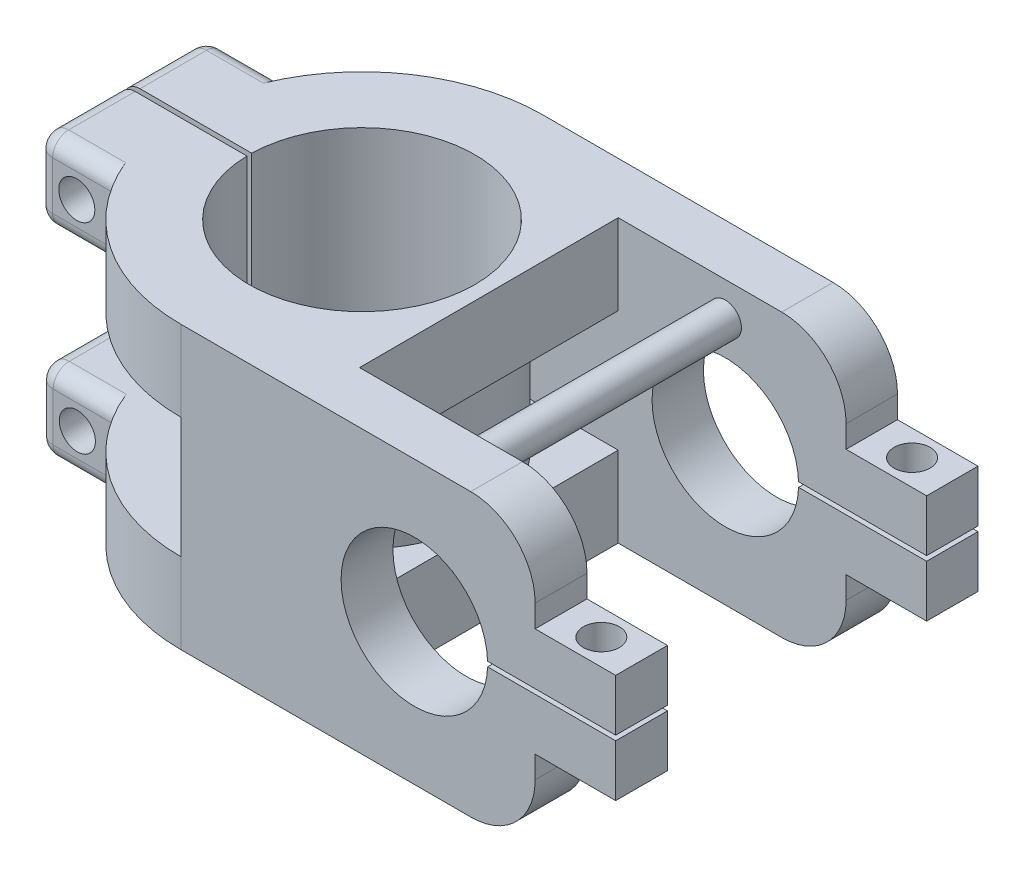
SolidWorks part; units mm, degrees
ref_plane "Front Plane" through (0, 0, 0) normal (0, 0, 1) x (1, 0, 0)
ref_plane "Top Plane" through (0, 0, 0) normal (0, 1, 0) x (1, 0, 0)
ref_plane "Right Plane" through (0, 0, 0) normal (1, 0, 0) x (0, 0, -1)
sketch "Sketch2" plane through (0, 0, 0) normal (0, 1, 0) x (1, 0, 0)
  circle A0 centre (0, 0) radius 17.78
  circle A2 centre (0, 0) radius 28.575
  dimension "D1" = 35.56
  dimension "D2" = 57.15
extrude "Boss-Extrude3" add sketch "Sketch2" along normal blind 12.7
sketch "Sketch3" plane through (0, 12.7, 0) normal (0, 1, 0) x (1, 0, 0)
  line L0 (0, 0) -> (20.2056, -20.2056) construction
  line L1 (0, 0) -> (20.2056, 20.2056) construction
  line L2 (0, 0) -> (-28.575, 0) construction
  line L3 (-25.3321, 0) -> (-25.3321, 13.2218) construction
  line L4 (-25.3321, 13.2218) -> (-25.3321, -13.2218)
  line L5 (-25.3321, 13.2218) -> (-36.1866, 13.2218)
  line L6 (-36.1866, 13.2218) -> (-36.1866, -13.2218)
  line L7 (-36.1866, -13.2218) -> (-25.3321, -13.2218)
  circle A0 centre (0, 0) radius 28.575 construction
extrude "Cut-Extrude1" cut sketch "Sketch3" against normal blind 12.7
sketch "Sketch4" plane through (0, 12.7, 0) normal (0, 1, 0) x (1, 0, 0)
  line L0 (0, 0) -> (-25.3321, 0) construction
  line L1 (-25.3321, -13.2218) -> (-25.3321, 13.2218) construction
  line L2 (-16.3768, 0) -> (-16.3768, 0.381)
  line L3 (-16.3768, 0) -> (-16.3768, -0.381)
  line L4 (-16.3768, 0.381) -> (-26.0036, 0.381)
  line L5 (-16.3768, -0.381) -> (-26.0036, -0.381)
  line L6 (-26.0036, -0.381) -> (-26.0036, 0.381)
  dimension "D1" = 0.762
extrude "Cut-Extrude2" cut sketch "Sketch4" against normal blind 12.7
sketch "Sketch5" plane through (-25.3321, 0, 0) normal (-1, 0, 0) x (0, 0, 1)
  line L1 (0.381, 12.7) -> (13.2218, 12.7)
  line L2 (0.381, 12.7) -> (0.381, 0)
  line L3 (0.381, 0) -> (13.2218, 0)
  line L4 (13.2218, 12.7) -> (13.2218, 0)
extrude "Boss-Extrude4" add sketch "Sketch5" along normal blind 12.7
sketch "Sketch6" plane through (-25.3321, 0, 0) normal (-1, 0, 0) x (0, 0, 1)
  line L1 (-13.2218, 12.7) -> (-0.381, 12.7)
  line L2 (-13.2218, 12.7) -> (-13.2218, 0)
  line L3 (-13.2218, 0) -> (-0.381, 0)
  line L4 (-0.381, 12.7) -> (-0.381, 0)
extrude "Boss-Extrude5" add sketch "Sketch6" along normal blind 12.7
sketch "Sketch7" plane through (0, 0, 13.2218) normal (0, 0, 1) x (1, 0, 0)
  line L0 (-31.6821, 12.7) -> (-31.6821, 0) construction
  line L1 (-38.0321, 12.7) -> (-25.3321, 12.7) construction
  line L2 (-38.0321, 0) -> (-25.3321, 0) construction
  circle A0 centre (-31.6821, 6.35) radius 2.8448
extrude "Cut-Extrude3" cut sketch "Sketch7" against normal blind 33.02
fillet "Fillet1" radius 2.54 1 edges at (-38.0321, 6.35, 13.2218)
fillet "Fillet2" radius 2.54 1 edges at (-38.0321, 6.35, -13.2218)
fillet "Fillet3" radius 2.54 3 edges at (-30.4121, 12.7, -13.2218) (-37.2882, 12.7, -12.4778) (-38.0321, 12.7, -5.5314)
fillet "Fillet4" radius 2.54 3 edges at (-30.4121, 12.7, 13.2218) (-37.2882, 12.7, 12.4778) (-38.0321, 12.7, 5.5314)
fillet "Fillet5" radius 2.54 3 edges at (-30.4121, 0, -13.2218) (-37.2882, 0, -12.4778) (-38.0321, 0, -5.5314)
fillet "Fillet6" radius 2.54 3 edges at (-30.4121, 0, 13.2218) (-37.2882, 0, 12.4778) (-38.0321, 0, 5.5314)
sketch "Sketch8" plane through (0, 12.7, 0) normal (0, 1, 0) x (1, 0, 0)
  circle A0 centre (0, 0) radius 18.7388
  circle A1 centre (0, 0) radius 17.78
extrude "Boss-Extrude6" add sketch "Sketch8" along normal blind 19.05
sketch "Sketch9" plane through (0, 31.75, 0) normal (0, 1, 0) x (1, 0, 0)
  circle A0 centre (0, 0) radius 28.575
extrude "Boss-Extrude7" add sketch "Sketch9" along normal blind 12.7
sketch "Sketch12" plane through (0, 44.45, 0) normal (0, 1, 0) x (1, 0, 0)
  line L0 (0, 0) -> (-28.575, 0) construction
  line L1 (-25.2365, 13.4034) -> (-25.2365, -13.4034)
  line L2 (-25.2365, 13.4034) -> (-36.6122, 13.4034)
  line L3 (-25.2365, -13.4034) -> (-36.6122, -13.4034)
  line L4 (-36.6122, -13.4034) -> (-36.6122, 13.4034)
  circle A0 centre (0, 0) radius 28.575 construction
extrude "Cut-Extrude4" cut sketch "Sketch12" against normal blind 12.7
sketch "Sketch13" plane through (-25.2365, 0, 0) normal (-1, 0, 0) x (0, 0, 1)
  line L0 (-18.7388, 31.75) -> (18.7388, 31.75) construction
  line L1 (-13.4034, 44.45) -> (13.4034, 44.45)
  line L2 (-13.4034, 44.45) -> (-13.4034, 31.75)
  line L3 (-13.4034, 31.75) -> (13.4034, 31.75)
  line L4 (13.4034, 44.45) -> (13.4034, 31.75)
  line L5 (13.4034, 31.75) -> (-13.4034, 31.75) construction
extrude "Boss-Extrude8" add sketch "Sketch13" along normal blind 12.7
sketch "Sketch14" plane through (0, 44.45, 0) normal (0, 1, 0) x (1, 0, 0)
  circle A0 centre (0, 0) radius 17.78
extrude "Cut-Extrude5" cut sketch "Sketch14" against normal blind 12.7
sketch "Sketch15" plane through (0, 44.45, 0) normal (0, 1, 0) x (1, 0, 0)
  line L0 (-37.9365, 0) -> (0, 0)
  line L1 (-37.9365, -13.4034) -> (-37.9365, 13.4034) construction
  line L2 (0, 0) -> (0, 0.381)
  line L3 (0, 0.381) -> (-38.0321, 0.381)
  line L4 (-38.0321, 0.381) -> (-37.9365, 0)
  line L5 (0, 0) -> (0, -0.381)
  line L6 (0, -0.381) -> (-37.9365, -0.381)
  line L7 (-37.9365, -0.381) -> (-37.9365, 0)
  line L8 (-37.9365, 0) -> (0, 0)
  circle M6 centre (0, 0) radius 17.78
  line M9 (-37.9365, 13.4034) -> (-37.9365, -13.4034)
  dimension "D1" = 0.381
extrude "Cut-Extrude6" cut sketch "Sketch15" against normal blind 12.7 contours L3 L0 M6 M9 region at (-27.8576, 44.45, -0.1905)
sketch "Sketch16" plane through (0, 44.45, 0) normal (0, 1, 0) x (1, 0, 0)
  line L6 (-37.9365, 0) -> (-16.9968, 0)
  line L7 (-37.9365, 0) -> (-37.9365, -0.381)
  line L8 (-37.9365, -0.381) -> (-16.9968, -0.381)
  line L9 (-16.9968, 0) -> (-16.9968, -0.381)
  dimension "D1" = 0.381
extrude "Cut-Extrude7" cut sketch "Sketch16" against normal blind 12.7
fillet "Fillet7" radius 2.54 1 edges at (-37.9365, 44.45, -6.8922)
fillet "Fillet8" radius 2.54 1 edges at (-37.9365, 44.45, 6.8922)
fillet "Fillet9" radius 2.54 1 edges at (-37.9365, 31.75, -6.8922)
fillet "Fillet10" radius 2.54 1 edges at (-37.9365, 31.75, 6.8922)
fillet "Fillet11" radius 2.54 5 edges at (-30.3165, 31.75, 13.4034) (-37.1925, 32.4939, 13.4034) (-30.3165, 44.45, 13.4034) (-37.1925, 43.7061, 13.4034) (-37.9365, 38.1, 13.4034)
fillet "Fillet12" radius 2.54 5 edges at (-30.3165, 44.45, -13.4034) (-37.1925, 43.7061, -13.4034) (-30.3165, 31.75, -13.4034) (-37.1925, 32.4939, -13.4034) (-37.9365, 38.1, -13.4034)
sketch "Sketch17" plane through (0, 0, 13.4034) normal (0, 0, 1) x (1, 0, 0)
  line L0 (-25.2365, 38.1) -> (-37.9365, 38.1) construction
  line L1 (-25.2365, 34.29) -> (-25.2365, 41.91) construction
  line L2 (-37.9365, 34.29) -> (-37.9365, 41.91) construction
  circle A0 centre (-31.5865, 38.1) radius 2.8448
extrude "Cut-Extrude8" cut sketch "Sketch17" against normal blind 29.464
sketch "Sketch19" plane through (0, 31.75, 0) normal (0, 1, 0) x (1, 0, 0)
  line L5 (-18.7349, 0.381) -> (-16.9078, 0.381)
  line L6 (-18.7349, 0.381) -> (-18.7349, -0.381)
  line L7 (-18.7349, -0.381) -> (-16.9078, -0.381)
  line L8 (-16.9078, 0.381) -> (-16.9078, -0.381)
extrude "Cut-Extrude13" cut sketch "Sketch19" against normal blind 29.464 body kept at (-35.3965, 31.75, -10.8634)
sketch "Sketch22" plane through (0, 12.7, 0) normal (0, 1, 0) x (1, 0, 0)
  line L0 (0, 0) -> (0, -18.7388) construction
  line L1 (0, -18.7388) -> (0, -20.3979) construction
  line L2 (0, -20.3979) -> (0, -28.575)
  line L3 (0, -28.575) -> (55.88, -28.575)
  line L4 (55.88, -28.575) -> (55.88, -20.3979)
  line L5 (55.88, -20.3979) -> (0, -20.3979)
  arc A0 (-18.7349, -0.381) -> (-18.7349, 0.381) centre (0, 0) ccw construction
  arc A1 (-26.5034, -10.6818) -> (-26.5034, 10.6818) centre (0, 0) ccw construction
  dimension "D1" = 55.88
extrude "Boss-Extrude12" add sketch "Sketch22" along normal blind 31.75 and the other way blind 12.7
sketch "Sketch23" plane through (0, 12.7, 0) normal (0, 1, 0) x (1, 0, 0)
  line L0 (0, -20.3979) -> (0, -18.6659) construction
  line L1 (0, 18.7388) -> (0, 20.4709) construction
  line L2 (0, 20.4709) -> (0, 28.575)
  line L3 (0, 28.575) -> (55.88, 28.575)
  line L4 (0, 20.4709) -> (55.88, 20.4709)
  line L5 (55.88, 20.4709) -> (55.88, 28.575)
  arc A0 (-18.7349, -0.381) -> (-18.7349, 0.381) centre (0, 0) ccw construction
  arc A1 (20.0114, -20.3979) -> (-26.5034, 10.6818) centre (0, 0) ccw construction
  dimension "D1" = 1.7321
  dimension "D2" = 55.88
extrude "Boss-Extrude13" add sketch "Sketch23" along normal blind 31.75 and the other way blind 12.7
sketch "Sketch24" plane through (0, 0, -28.575) normal (0, 0, -1) x (-1, 0, 0)
  line L0 (-17.78, 22.225) -> (-55.88, 22.225) construction
  line L2 (-17.78, 44.45) -> (-17.78, 0) construction
  line L3 (-55.88, 44.45) -> (0, 44.45) construction
  line L4 (-55.88, 0) -> (-55.88, 44.45) construction
  circle A0 centre (-36.83, 22.225) radius 11.557
extrude "Cut-Extrude14" cut sketch "Sketch24" against normal blind 67.31
fillet "Fillet13" radius 10.16 1 edges at (55.88, 44.45, 24.4865)
fillet "Fillet14" radius 10.16 1 edges at (55.88, 0, 24.4865)
fillet "Fillet15" radius 10.16 1 edges at (55.88, 44.45, -24.5229)
fillet "Fillet16" radius 10.16 1 edges at (55.88, 0, -24.5229)
sketch "Sketch25" plane through (0, 44.45, 0) normal (0, 1, 0) x (1, 0, 0)
  line L0 (28.575, 0.0522) -> (28.575, 20.4709)
  line L1 (19.9368, 20.4709) -> (45.72, 20.4709) construction
  line L2 (28.575, 20.4709) -> (19.9368, 20.4709)
  line L3 (19.9368, 20.4709) -> (20.0114, -20.3979)
  line L4 (20.0114, -20.3979) -> (28.575, -20.3979)
  line L5 (45.72, -20.3979) -> (20.0114, -20.3979) construction
  line L6 (28.575, -20.3979) -> (28.575, 0.0522)
  arc A0 (20.0114, -20.3979) -> (19.9368, 20.4709) centre (0, 0) ccw construction
extrude "Cut-Extrude15" cut sketch "Sketch25" against normal blind 67.31 body kept at (55.88, 10.16, -20.4709)
sketch "Sketch26" plane through (0, 0, -20.4709) normal (0, 0, 1) x (1, 0, 0)
  line L0 (36.83, 33.782) -> (36.83, 44.45) construction
  line L1 (19.9368, 44.45) -> (45.72, 44.45) construction
  circle A0 centre (36.83, 22.225) radius 11.557 construction
  circle A1 centre (36.83, 39.116) radius 2.54
extrude "Boss-Extrude14" add sketch "Sketch26" along normal blind 43.434
sketch "Sketch27" plane through (0, 0, 28.575) normal (0, 0, 1) x (1, 0, 0)
  line L0 (48.387, 22.225) -> (55.88, 22.225) construction
  line L1 (55.88, 10.16) -> (55.88, 34.29) construction
  line L2 (57.8595, 22.225) -> (46.9704, 22.225)
  line L3 (46.9704, 22.225) -> (46.9704, 22.606)
  line L4 (46.9704, 22.606) -> (57.8595, 22.606)
  line L5 (57.8595, 22.606) -> (57.8595, 22.225)
  circle A0 centre (36.83, 22.225) radius 11.557 construction
  dimension "D1" = 0.381
extrude "Cut-Extrude16" cut sketch "Sketch27" against normal blind 64.516
sketch "Sketch28" plane through (0, 0, 28.575) normal (0, 0, 1) x (1, 0, 0)
  line L0 (47.571, 22.225) -> (56.4711, 22.225)
  line L1 (56.4711, 22.225) -> (56.4711, 21.844)
  line L2 (56.4711, 21.844) -> (47.571, 21.844)
  line L3 (47.571, 21.844) -> (47.571, 22.225)
  dimension "D1" = 0.381
extrude "Cut-Extrude17" cut sketch "Sketch28" against normal blind 64.516
sketch "Sketch29" plane through (55.88, 0, 0) normal (1, 0, 0) x (0, 0, -1)
  line L0 (-28.575, 22.606) -> (-20.3979, 22.606)
  line L1 (-20.3979, 22.606) -> (-20.3979, 30.7831)
  line L2 (-20.3979, 22.606) -> (-20.3979, 34.29) construction
  line L3 (-20.3979, 30.7831) -> (-28.575, 30.7831)
  line L4 (-28.575, 22.606) -> (-28.575, 34.29) construction
  line L5 (-28.575, 30.7831) -> (-28.575, 22.606)
  dimension "D1" = 8.1771
extrude "Boss-Extrude15" add sketch "Sketch29" along normal blind 12.7
sketch "Sketch30" plane through (55.88, 0, 0) normal (1, 0, 0) x (0, 0, -1)
  line L0 (-28.575, 21.844) -> (-20.3979, 21.844)
  line L1 (-20.3979, 21.844) -> (-20.3979, 13.6669)
  line L2 (-20.3979, 10.16) -> (-20.3979, 21.844) construction
  line L3 (-20.3979, 13.6669) -> (-28.575, 13.6669)
  line L4 (-28.575, 10.16) -> (-28.575, 21.844) construction
  line L5 (-28.575, 13.6669) -> (-28.575, 21.844)
extrude "Boss-Extrude16" add sketch "Sketch30" along normal blind 12.7
sketch "Sketch31" plane through (0, 30.7831, 0) normal (0, 1, 0) x (1, 0, 0)
  line L0 (62.23, -20.3979) -> (62.23, -28.575) construction
  line L1 (68.58, -20.3979) -> (55.88, -20.3979) construction
  line L2 (68.58, -28.575) -> (55.88, -28.575) construction
  circle A0 centre (62.23, -24.4865) radius 2.8448
extrude "Cut-Extrude18" cut sketch "Sketch31" against normal blind 22.098
sketch "Sketch34" plane through (55.88, 0, 0) normal (1, 0, 0) x (0, 0, -1)
  line L0 (28.575, 22.606) -> (28.575, 30.7831)
  line L1 (28.575, 22.606) -> (28.575, 34.29) construction
  line L2 (28.575, 30.7831) -> (20.4709, 30.7831)
  line L3 (20.4709, 22.606) -> (20.4709, 34.29) construction
  line L4 (20.4709, 30.7831) -> (20.4709, 22.606)
  line L5 (20.4709, 22.606) -> (28.575, 22.606)
extrude "Boss-Extrude17" add sketch "Sketch34" along normal blind 12.7
sketch "Sketch35" plane through (55.88, 0, 0) normal (1, 0, 0) x (0, 0, -1)
  line L0 (28.575, 21.844) -> (28.575, 13.6669)
  line L1 (28.575, 10.16) -> (28.575, 21.844) construction
  line L2 (28.575, 13.6669) -> (20.4709, 13.6669)
  line L3 (20.4709, 10.16) -> (20.4709, 21.844) construction
  line L4 (20.4709, 13.6669) -> (20.4709, 21.844)
  line L5 (20.4709, 21.844) -> (28.575, 21.844)
extrude "Boss-Extrude18" add sketch "Sketch35" along normal blind 12.7
sketch "Sketch36" plane through (0, 30.7831, 0) normal (0, 1, 0) x (1, 0, 0)
  line L0 (62.23, 28.575) -> (62.23, 20.4709) construction
  line L1 (68.58, 28.575) -> (55.88, 28.575) construction
  line L2 (68.58, 20.4709) -> (55.88, 20.4709) construction
  circle A0 centre (62.23, 24.5229) radius 2.8448
extrude "Cut-Extrude19" cut sketch "Sketch36" against normal blind 27.686
